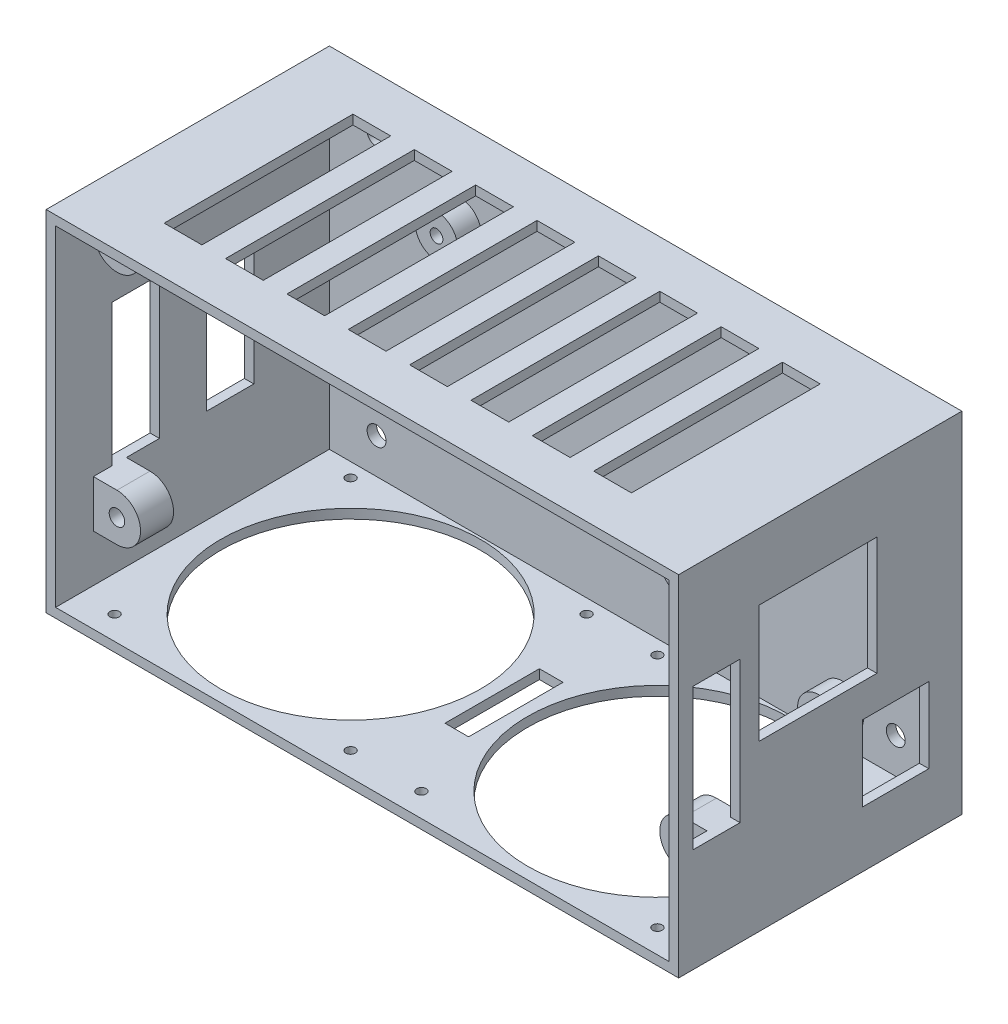
SolidWorks part; units mm, degrees
material "ABS"
ref_plane "Plano frontal" through (0, 0, 0) normal (0, 0, 1) x (1, 0, 0)
ref_plane "Plano superior" through (0, 0, 0) normal (0, 1, 0) x (1, 0, 0)
ref_plane "Plano direito" through (0, 0, 0) normal (1, 0, 0) x (0, 0, -1)
sketch "Esboço1" plane through (0, 0, 0) normal (0, 0, 1) x (1, 0, 0)
  line L0 (-67, 37) -> (67, 37)
  line L1 (-65, 35) -> (65, 35)
  line L2 (-65, 35) -> (-65, -35)
  line L3 (-65, -35) -> (65, -35)
  line L4 (65, 35) -> (65, -35)
  line L5 (-65, 35) -> (65, -35) construction
  line L6 (-65, -35) -> (65, 35) construction
  line L7 (67, 37) -> (67, -37)
  line L8 (-67, -37) -> (67, -37)
  line L9 (-67, 37) -> (-67, -37)
  point P0 (0, 0)
  dimension "D2" = 130
  dimension "D3" = 70
  dimension "D1" = 2
extrude "Ressalto-extrusão1" add sketch "Esboço1" along normal blind 60
sketch "Esboço2" plane through (0, 0, 0) normal (0, 0, -1) x (-1, 0, 0)
  line L0 (-67, -37) -> (-67, 37) construction
  line L1 (67, -37) -> (-67, -37) construction
  line L2 (-67, 37) -> (67, 37) construction
  line L3 (67, 37) -> (67, -37) construction
  line L4 (-67, -37) -> (-67, 37)
  line L5 (67, -37) -> (-67, -37)
  line L6 (-67, 37) -> (67, 37)
  line L7 (67, 37) -> (67, -37)
  line L8 (55, 27.5) -> (-55, 27.5) construction
  line L9 (-55, 27.5) -> (-55, -27.5) construction
  line L10 (-55, -27.5) -> (55, -27.5) construction
  line L11 (55, -27.5) -> (55, 27.5) construction
  circle A0 centre (-55, -27.5) radius 2
  circle A1 centre (55, -27.5) radius 2
  circle A2 centre (55, 27.5) radius 2
  circle A3 centre (-55, 27.5) radius 2
  point P12 (0, 27.5)
  point P13 (0, 37)
  point P14 (-55, 0)
  point P15 (-67, 0)
  dimension "D1" = 4
  dimension "D2" = 110
  dimension "D3" = 55
extrude "Ressalto-extrusão2" add sketch "Esboço2" against normal blind 2
sketch "Esboço3" plane through (67, 0, 0) normal (1, 0, 0) x (0, 0, -1)
  line L0 (-60, -37) -> (0, -37) construction
  line L1 (-43, 22.9) -> (-18, 22.9)
  line L2 (-43, 22.9) -> (-43, -2.1)
  line L3 (-43, -2.1) -> (-18, -2.1)
  line L4 (-18, 22.9) -> (-18, -2.1)
  line L5 (-21, -9.1) -> (-7, -9.1)
  line L6 (-21, -9.1) -> (-21, -25.1)
  line L7 (-21, -25.1) -> (-7, -25.1)
  line L8 (-7, -9.1) -> (-7, -25.1)
  line L11 (-60, -37) -> (-60, 37) construction
  line L12 (-57, 15) -> (-47, 15)
  line L13 (-57, 15) -> (-57, -15)
  line L14 (-57, -15) -> (-47, -15)
  line L15 (-47, 15) -> (-47, -15)
  line L16 (-57, 15) -> (-47, -15) construction
  line L17 (-57, -15) -> (-47, 15) construction
  line L18 (0, -37) -> (0, 37) construction
  point P14 (-52, 0)
  point P23 (-60, 0)
  dimension "D1" = 16
  dimension "D2" = 14
  dimension "D3" = 11.9
  dimension "D4" = 7
  dimension "D5" = 25
  dimension "D6" = 25
  dimension "D7" = 7
  dimension "D8" = 18
  dimension "D9" = 8
  dimension "D10" = 30
  dimension "D11" = 10
extrude "USB + fonte" cut sketch "Esboço3" against normal blind 10
sketch "Esboço6" plane through (0, -37, 0) normal (0, -1, 0) x (1, 0, 0)
  line L1 (-52, 50) -> (-44, 50)
  line L2 (-52, 50) -> (-52, 10)
  line L3 (-52, 10) -> (-44, 10)
  line L4 (-44, 50) -> (-44, 10)
  line L5 (-67, 60) -> (-67, 0) construction
  line L6 (-39, 50) -> (-31, 50)
  line L7 (-39, 50) -> (-39, 10)
  line L8 (-39, 10) -> (-31, 10)
  line L9 (-31, 50) -> (-31, 10)
  line L10 (-26, 50) -> (-18, 50)
  line L11 (-26, 50) -> (-26, 10)
  line L12 (-26, 10) -> (-18, 10)
  line L13 (-18, 50) -> (-18, 10)
  line L14 (-13, 50) -> (-5, 50)
  line L15 (-13, 50) -> (-13, 10)
  line L16 (-13, 10) -> (-5, 10)
  line L17 (-5, 50) -> (-5, 10)
  line L18 (0, 50) -> (8, 50)
  line L19 (0, 50) -> (0, 10)
  line L20 (0, 10) -> (8, 10)
  line L21 (8, 50) -> (8, 10)
  line L22 (13, 50) -> (21, 50)
  line L23 (13, 50) -> (13, 10)
  line L24 (13, 10) -> (21, 10)
  line L25 (21, 50) -> (21, 10)
  line L26 (26, 50) -> (34, 50)
  line L27 (26, 50) -> (26, 10)
  line L28 (26, 10) -> (34, 10)
  line L29 (34, 50) -> (34, 10)
  line L30 (39, 50) -> (47, 50)
  line L31 (39, 50) -> (39, 10)
  line L32 (39, 10) -> (47, 10)
  line L33 (47, 50) -> (47, 10)
  line L34 (67, 60) -> (67, 0) construction
  point P4 (-52, 30)
  point P37 (67, 30)
  dimension "D1" = 8
  dimension "D2" = 40
  dimension "D4" = 15
  dimension "D5" = 8
extrude "saida de ar" cut sketch "Esboço6" against normal through all from offset 20 offset against normal yes
sketch "Esboço7" plane through (-67, 0, 0) normal (-1, 0, 0) x (0, 0, 1)
  line L1 (48, 15) -> (38, 15)
  line L2 (48, 15) -> (48, -15)
  line L3 (48, -15) -> (38, -15)
  line L4 (38, 15) -> (38, -15)
  line L5 (48, 15) -> (38, -15) construction
  line L6 (48, -15) -> (38, 15) construction
  line L7 (28, 15) -> (18, 15)
  line L8 (28, 15) -> (28, -15)
  line L9 (28, -15) -> (18, -15)
  line L10 (18, 15) -> (18, -15)
  line L11 (28, 15) -> (18, -15) construction
  line L12 (28, -15) -> (18, 15) construction
  line L13 (0, 37) -> (0, -37) construction
  point P0 (43, 0)
  point P5 (23, 0)
  dimension "D1" = 10
  dimension "D2" = 30
  dimension "D3" = 10
  dimension "D4" = 18
extrude "display" cut sketch "Esboço7" against normal blind 12
sketch "Esboço8" plane through (0, 0, 2) normal (0, 0, -1) x (-1, 0, 0)
  line L0 (-65, -35) -> (-65, 35) construction
  line L1 (-65, 35) -> (65, 35) construction
  circle A0 centre (-43.7, -27.67) radius 4.5
  circle A1 centre (-43.7, -27.67) radius 1.35
  circle A2 centre (37.3, 20.5) radius 4.5
  circle A3 centre (37.3, 20.5) radius 1.35
  circle A4 centre (-45, 20.5) radius 1.35
  circle A5 centre (-45, 20.5) radius 1.35
  circle A6 centre (-45, 20.5) radius 4.5
  dimension "D1" = 9
  dimension "D2" = 2.7
  dimension "D3" = 82.3
  dimension "D4" = 48.17
  dimension "D5" = 1.3
  dimension "D6" = 20
  dimension "D7" = 14.5
extrude "Ressalto-extrusão3" add sketch "Esboço8" against normal blind 5 contours A2 A3 | A6 A4 | A0 A1 region at (48.0727, -27.67, 2) region at (-32.9273, 20.5, 2) region at (49.3727, 20.5, 2)
extrude "Corte-extrusão4" cut sketch "Esboço8<3>" along normal through all contours A4 | A3 | A1
sketch "Esboço8<3>" plane through (0, 0, 2) normal (0, 0, -1) x (-1, 0, 0) same geometry as "Esboço8"
sketch "Esboço9" plane through (0, 0, 2) normal (0, 0, 1) x (1, 0, 0)
  circle A0 centre (45, 20.5) radius 3
  circle A1 centre (43.7, -27.67) radius 3
  circle A2 centre (-37.3, 20.5) radius 3
  circle A3 centre (43.7, -27.67) radius 1.35 construction
  dimension "D1" = 6
extrude "Corte-extrusão5" cut sketch "Esboço9" along normal offset from surface 3 and the other way blind 10 up to face at (-32.8, 20.5, 7)
sketch "Esboço10" plane through (0, 37, 0) normal (0, 1, 0) x (1, 0, 0)
  line L0 (32.5, -30) -> (-32.5, -30) construction
  line L1 (67, -60) -> (-67, -60) construction
  line L2 (67, -60) -> (67, 0) construction
  line L4 (7.5, -5) -> (57.5, -5) construction
  line L5 (7.5, -5) -> (7.5, -55) construction
  line L6 (7.5, -55) -> (57.5, -55) construction
  line L7 (57.5, -5) -> (57.5, -55) construction
  line L8 (7.5, -5) -> (57.5, -55) construction
  line L9 (7.5, -55) -> (57.5, -5) construction
  line L10 (-57.5, -5) -> (-7.5, -5) construction
  line L11 (-57.5, -5) -> (-57.5, -55) construction
  line L12 (-57.5, -55) -> (-7.5, -55) construction
  line L13 (-7.5, -5) -> (-7.5, -55) construction
  line L14 (-57.5, -5) -> (-7.5, -55) construction
  line L15 (-57.5, -55) -> (-7.5, -5) construction
  line L16 (-2.5, -20) -> (2.5, -20)
  line L17 (-2.5, -20) -> (-2.5, -40)
  line L18 (-2.5, -40) -> (2.5, -40)
  line L19 (2.5, -20) -> (2.5, -40)
  line L20 (-2.5, -20) -> (2.5, -40) construction
  line L21 (-2.5, -40) -> (2.5, -20) construction
  circle A0 centre (32.5, -30) radius 27.5
  circle A1 centre (-32.5, -30) radius 27.5
  circle A2 centre (-57.5, -55) radius 1
  circle A3 centre (-7.5, -55) radius 1
  circle A4 centre (7.5, -55) radius 1
  circle A5 centre (57.5, -55) radius 1
  circle A6 centre (57.5, -5) radius 1
  circle A7 centre (7.5, -5) radius 1
  circle A8 centre (-7.5, -5) radius 1
  circle A9 centre (-57.5, -5) radius 1
  point P4 (0, -30)
  point P7 (0, -60)
  point P10 (67, -30)
  point P27 (0, -30)
  dimension "D2" = 55
  dimension "D3" = 2
  dimension "D1" = 65
  dimension "D4" = 50
  dimension "D5" = 5
  dimension "D6" = 20
extrude "cooler" cut sketch "Esboço10" against normal through all from vertex starting at point (-65, -35, 2)
sketch "Esboço11" plane through (0, 0, 60) normal (0, 0, 1) x (1, 0, 0)
  line L0 (-65, 35) -> (-65, -35) construction
  line L1 (65, -25) -> (60, -25)
  line L2 (65, -25) -> (65, -15)
  line L3 (65, 35) -> (60, 35)
  line L4 (-65, -25) -> (-65, -15)
  line L5 (65, -25) -> (-65, 35) construction
  line L6 (65, 35) -> (-65, -25) construction
  line L7 (-67, 37) -> (-67, -37) construction
  line L8 (60, 30) -> (-60, 30) construction
  line L9 (60, 30) -> (60, -20) construction
  line L10 (60, -20) -> (-60, -20) construction
  line L11 (-60, 30) -> (-60, -20) construction
  line L12 (60, 30) -> (-60, -20) construction
  line L13 (60, -20) -> (-60, 30) construction
  line L14 (67, 37) -> (-67, 37) construction
  line L15 (-60, 35) -> (-65, 35)
  line L16 (-65, 30) -> (-65, 35)
  line L17 (65, 30) -> (65, 35)
  line L18 (-60, -25) -> (-65, -25)
  line L19 (65, -35) -> (65, 35) construction
  line L20 (-60, -15) -> (-65, -15)
  line L21 (-65, 35) -> (-65, -35) construction
  line L22 (60, -15) -> (65, -15)
  line L23 (65, -35) -> (65, 35) construction
  arc A0 (-65, 30) -> (-60, 35) centre (-60, 30) ccw
  circle A1 centre (-60, 30) radius 1.65
  arc A2 (60, 35) -> (65, 30) centre (60, 30) ccw
  circle A3 centre (60, 30) radius 1.65
  circle A5 centre (60, -20) radius 1.65
  arc A6 (-60, -25) -> (-60, -15) centre (-60, -20) ccw
  circle A7 centre (-60, -20) radius 1.65
  arc A8 (60, -15) -> (60, -25) centre (60, -20) ccw
  point P0 (0, 0)
  point P10 (0, 0)
  point P28 (-60, -25)
  point P29 (65, 30)
  point P40 (-60, -25)
  dimension "D3" = 3.3
  dimension "D1" = 7
  dimension "D2" = 7
  dimension "D4" = 120
  dimension "D5" = 50
extrude "Ressalto-extrusão4" add sketch "Esboço11" against normal blind 7 from offset 8 offset against normal yes
equation "\"D2@Esboço11\"=\"D1@Esboço11\""
